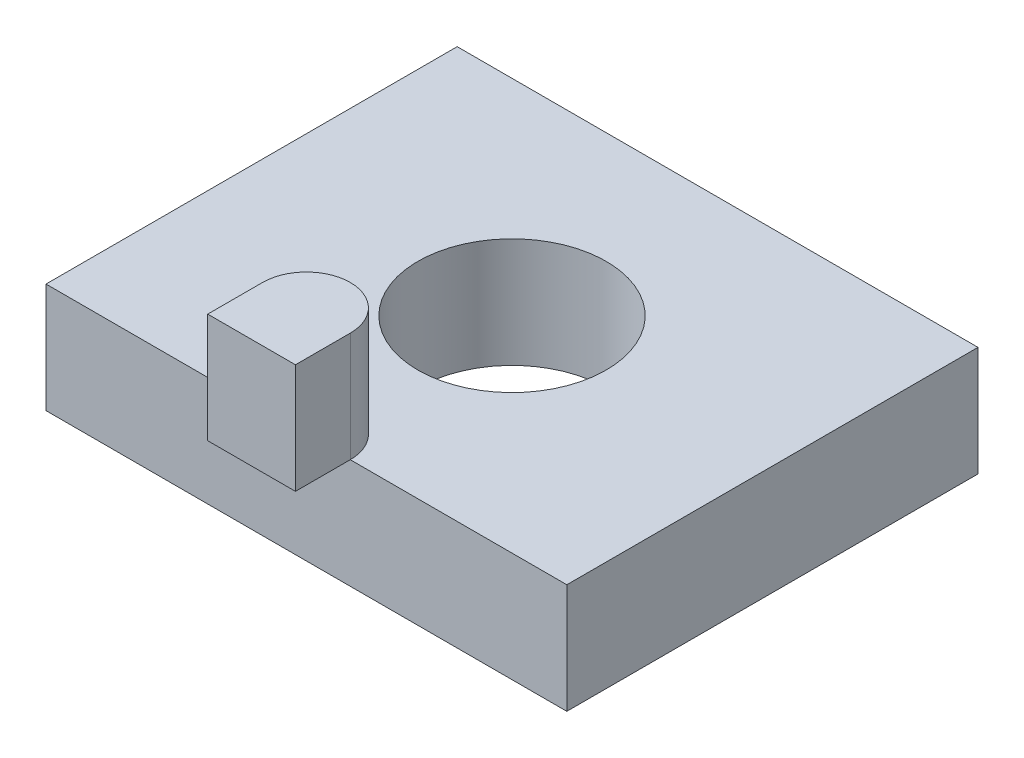
SolidWorks part; units mm, degrees
ref_plane "Front Plane" through (0, 0, 0) normal (0, 0, 1) x (1, 0, 0)
ref_plane "Top Plane" through (0, 0, 0) normal (0, 1, 0) x (1, 0, 0)
ref_plane "Right Plane" through (0, 0, 0) normal (1, 0, 0) x (0, 0, -1)
sketch "Sketch1" plane through (0, 0, 0) normal (0, 1, 0) x (1, 0, 0)
  line L1 (-47.5, 37.5) -> (47.5, 37.5)
  line L2 (-47.5, 37.5) -> (-47.5, -37.5)
  line L3 (-47.5, -37.5) -> (47.5, -37.5)
  line L4 (47.5, 37.5) -> (47.5, -37.5)
  line L5 (-47.5, 37.5) -> (47.5, -37.5) construction
  line L6 (-47.5, -37.5) -> (47.5, 37.5) construction
  point P0 (0, 0)
  dimension "D1" = 95
  dimension "D2" = 75
extrude "Boss-Extrude1" add sketch "Sketch1" along normal mid plane 20
sketch "Sketch2" plane through (0, 0, 37.5) normal (0, 0, 1) x (1, 0, 0)
  line L0 (0, 10) -> (0, 30)
  line L1 (-47.5, 10) -> (47.5, 10) construction
  line L2 (0, 30) -> (-8, 30)
  line L3 (-8, 30) -> (-8, 10)
  line L4 (-8, 10) -> (0, 10)
  dimension "D1" = 8
  dimension "D2" = 20
revolve "Revolve1" add sketch "Sketch2" angle 180 about L0 reverse direction yes
sketch "Sketch3" plane through (0, 0, 37.5) normal (0, 0, 1) x (1, 0, 0)
  line L1 (-8, 30) -> (8, 30)
  line L2 (-8, 30) -> (-8, 10)
  line L3 (-8, 10) -> (8, 10)
  line L4 (8, 30) -> (8, 10)
  line L5 (-8, 30) -> (8, 10) construction
  line L6 (-8, 10) -> (8, 30) construction
  point P4 (0, 20)
extrude "Boss-Extrude2" add sketch "Sketch3" along normal blind 10
sketch "Sketch4" plane through (0, 10, 0) normal (0, 1, 0) x (1, 0, 0)
  circle A0 centre (0, 0) radius 17.1789
extrude "Cut-Extrude1" cut sketch "Sketch4" against normal through all
